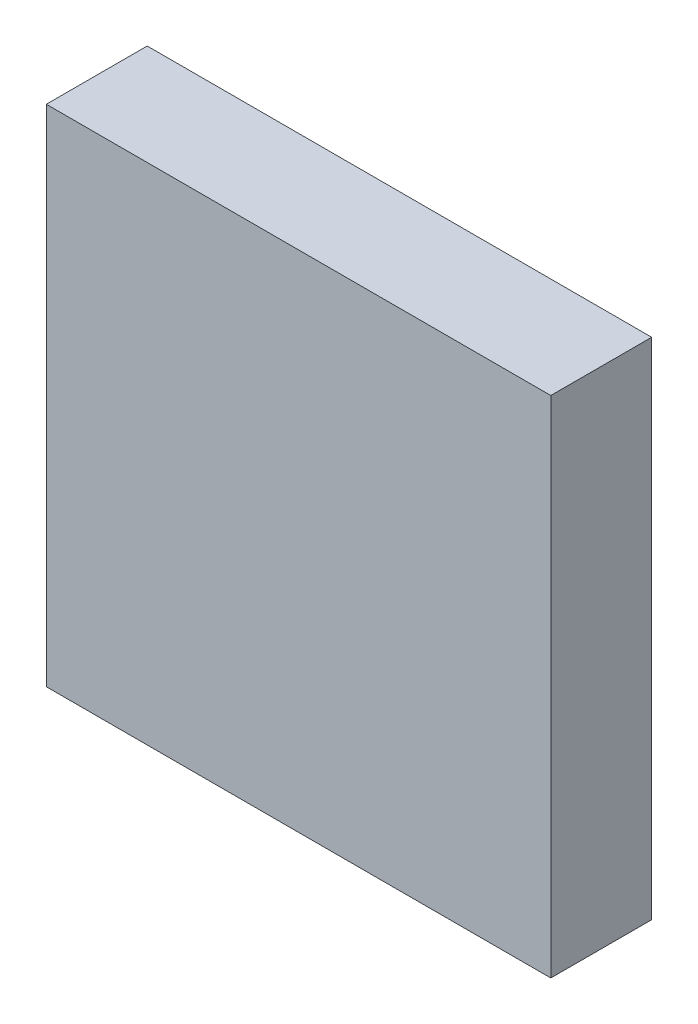
SolidWorks part; units mm, degrees
ref_plane "Front Plane" through (0, 0, 0) normal (0, 0, 1) x (1, 0, 0)
ref_plane "Top Plane" through (0, 0, 0) normal (0, 1, 0) x (1, 0, 0)
ref_plane "Right Plane" through (0, 0, 0) normal (1, 0, 0) x (0, 0, -1)
sketch "Esboço1" plane through (0, 0, 0) normal (0, 0, 1) x (1, 0, 0)
  line L0 (0, 50) -> (0, -50) construction
  line L1 (-50, 50) -> (50, 50)
  line L2 (-50, 50) -> (-50, -50)
  line L3 (-50, -50) -> (50, -50)
  line L4 (50, 50) -> (50, -50)
  point P6 (0, 0)
  dimension "D1" = 100
  dimension "D2" = 100
extrude "Ressalto-extrusão1" add sketch "Esboço1" along normal blind 20
sketch "Esboço2" plane through (0, 0, 0) normal (0, 0, -1) x (-1, 0, 0)
  line L16 (50, 0) -> (-50, 0) construction
  line L17 (50, 50) -> (50, -50) construction
  line L18 (-50, -50) -> (-50, 50) construction
  line L19 (0, 50) -> (0, -50) construction
  line L20 (-34, -16) -> (-16, -16)
  line L21 (-34, -34) -> (-34, -16)
  line L22 (-16, -34) -> (-34, -34)
  line L23 (-16, -16) -> (-16, -34)
  line L24 (16, -16) -> (16, -34)
  line L25 (34, -16) -> (16, -16)
  line L26 (16, -34) -> (34, -34)
  line L27 (34, -34) -> (34, -16)
  line L28 (-50, 50) -> (50, 50) construction
  line L29 (50, -50) -> (-50, -50) construction
  line L30 (-34, 34) -> (-34, 16)
  line L31 (-16, 34) -> (-34, 34)
  line L32 (-16, 16) -> (-16, 34)
  line L33 (-34, 16) -> (-16, 16)
  line L34 (34, 16) -> (16, 16)
  line L35 (34, 34) -> (34, 16)
  line L36 (16, 34) -> (34, 34)
  line L37 (16, 16) -> (16, 34)
extrude "Ressalto-extrusão2" add sketch "Esboço2" along normal blind 10
